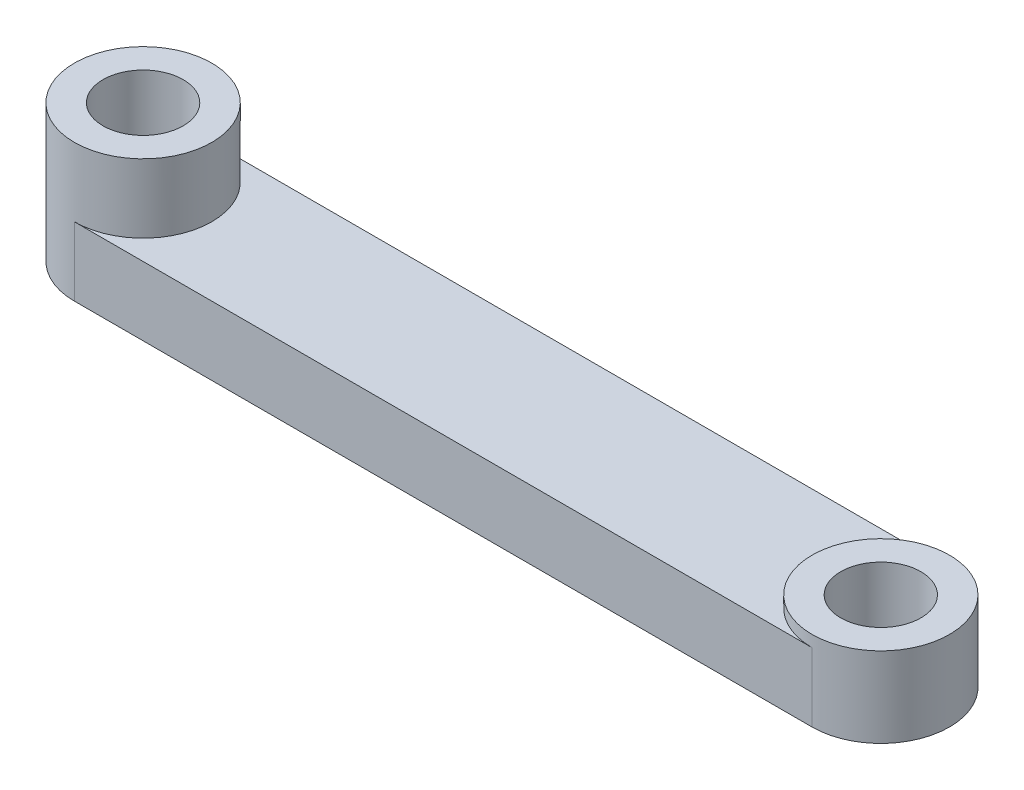
SolidWorks part; units mm, degrees
material "PET"
ref_plane "Спереди" through (0, 0, 0) normal (0, 0, 1) x (1, 0, 0)
ref_plane "Сверху" through (0, 0, 0) normal (0, 1, 0) x (1, 0, 0)
ref_plane "Справа" through (0, 0, 0) normal (1, 0, 0) x (0, 0, -1)
sketch "Эскиз1" plane through (0, 0, 0) normal (0, 1, 0) x (1, 0, 0)
  line L0 (0, 0) -> (32.2, 0) construction
  line L1 (0, 3) -> (32.2, 3)
  line L2 (0, -3) -> (32.2, -3)
  arc A2 (0, 3) -> (0, -3) centre (0, 0) ccw
  arc A3 (32.2, -3) -> (32.2, 3) centre (32.2, 0) ccw
  point P3 (16.1, 0)
  dimension "D1" = 3
  dimension "D2" = 32.2
extrude "Бобышка-Вытянуть1" add sketch "Эскиз1" along normal blind 3
sketch "Эскиз2" plane through (0, 3, 0) normal (0, 1, 0) x (1, 0, 0)
  circle A0 centre (32.2, 0) radius 3
extrude "Бобышка-Вытянуть2" add sketch "Эскиз2" along normal blind 0.5
sketch "Эскиз3" plane through (0, 3, 0) normal (0, 1, 0) x (1, 0, 0)
  circle A0 centre (0, 0) radius 3
extrude "Бобышка-Вытянуть3" add sketch "Эскиз3" along normal blind 3
sketch "Эскиз4" plane through (0, 6, 0) normal (0, 1, 0) x (1, 0, 0)
  circle A0 centre (0, 0) radius 1.75
  circle A1 centre (32.2, 0) radius 1.75
  dimension "D1" = 3.5
  dimension "D2" = 3.5
extrude "Вырез-Вытянуть1" cut sketch "Эскиз4" against normal through all
